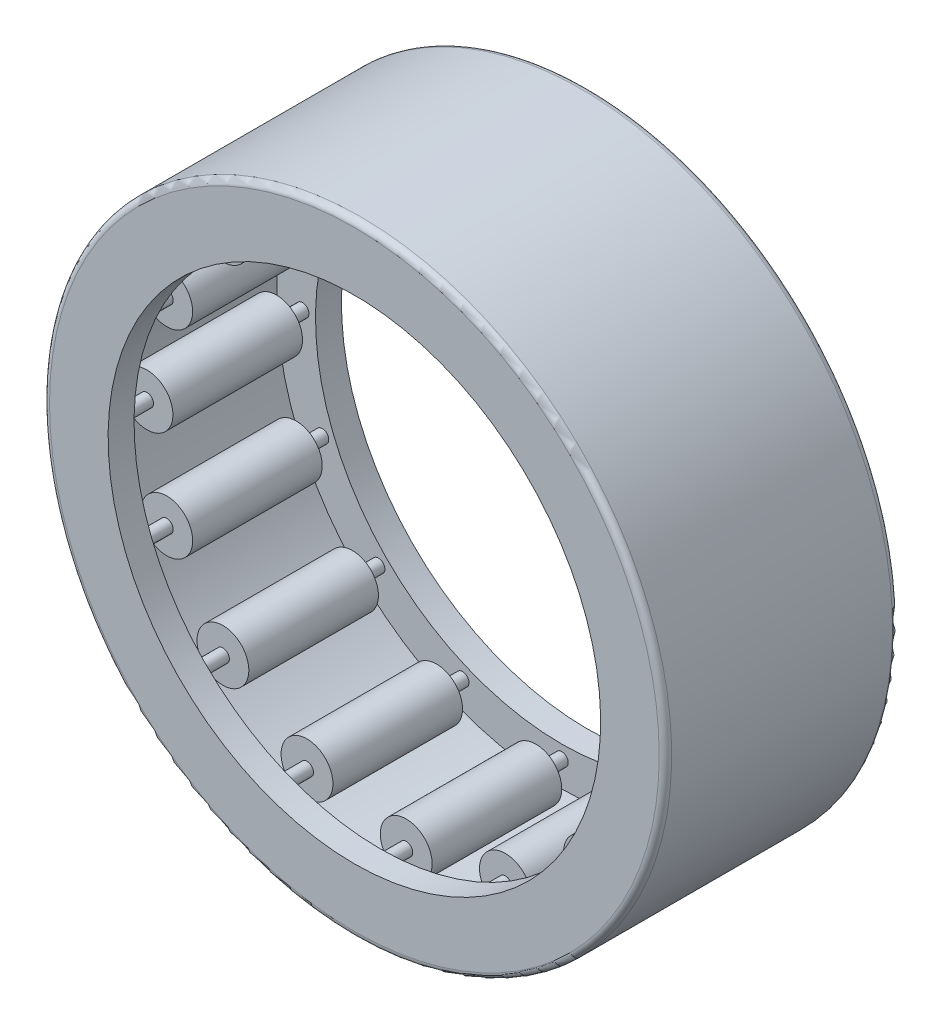
SolidWorks part; units mm, degrees
ref_plane "Front Plane" through (0, 0, 0) normal (0, 0, 1) x (1, 0, 0)
ref_plane "Top Plane" through (0, 0, 0) normal (0, 1, 0) x (1, 0, 0)
ref_plane "Right Plane" through (0, 0, 0) normal (1, 0, 0) x (0, 0, -1)
sketch "Sketch1" plane through (0, 0, 0) normal (1, 0, 0) x (0, 0, -1)
  line L0 (-4.7625, 0) -> (4.7625, 0) construction
  line L1 (0, 0) -> (0, 12.7) construction
  line L2 (-4.7625, 0) -> (-4.7625, 12.7) construction
  line L3 (-4.7625, 12.7) -> (4.7625, 12.7)
  line L4 (4.7625, 12.7) -> (4.7625, 0) construction
  line L5 (4.7625, 0) -> (3.7042, 0) construction
  line L6 (3.7042, 0) -> (3.7042, 11.6417) construction
  line L7 (3.7042, 11.6417) -> (-3.7042, 11.6417)
  line L8 (-3.7042, 11.6417) -> (-3.7042, 0) construction
  line L9 (-3.7042, 0) -> (-4.7625, 0) construction
  line L10 (-4.7625, 12.7) -> (-4.7625, 10.0542)
  line L11 (-4.7625, 10.0542) -> (-3.7042, 10.0542)
  line L12 (-3.7042, 10.0542) -> (-3.7042, 11.6417)
  line L13 (3.7042, 12.7) -> (3.7042, 11.6417) construction
  line L14 (3.7042, 11.6417) -> (3.7042, 10.0542)
  line L15 (3.7042, 10.0542) -> (4.7625, 10.0542)
  line L16 (4.7625, 10.0542) -> (4.7625, 12.7)
  line L17 (3.7042, 11.6417) -> (3.7042, 10.5833) construction
  line L18 (3.7042, 10.5833) -> (3.7042, 9.525) construction
  point P5 (0, 9.525)
  dimension "Width" = 9.525
  dimension "OD" = 25.4
  dimension "Shaft Dia" = 19.05
revolve "Revolve1" add sketch "Sketch1" angle 360 about L0
sketch "Sketch2" plane through (0, 0, 0) normal (1, 0, 0) x (0, 0, -1)
  line L0 (3.7042, 11.6417) -> (-3.7042, 11.6417) construction
  line L1 (-2.6458, 10.5833) -> (2.6458, 10.5833) construction
  line L2 (-2.6458, 10.5833) -> (-2.6458, 11.6417) construction
  line L3 (-2.6458, 11.6417) -> (2.6458, 11.6417)
  line L4 (2.6458, 10.5833) -> (2.6458, 11.6417) construction
  line L5 (3.7042, 10.0542) -> (4.7625, 10.0542) construction
  line L6 (-3.7042, 10.5833) -> (-2.6458, 10.5833) construction
  line L7 (2.6458, 10.5833) -> (3.7042, 10.5833) construction
  line L8 (-4.7625, 10.0542) -> (-3.7042, 10.0542) construction
  line L9 (-2.6458, 10.8479) -> (-2.6458, 10.3187) construction
  line L10 (-3.7042, 10.5833) -> (-3.7042, 10.0542) construction
  line L11 (-2.6458, 11.6417) -> (-2.6458, 10.8479)
  line L12 (2.6458, 11.6417) -> (2.6458, 10.8479)
  line L13 (2.6458, 10.8479) -> (-2.6458, 10.8479)
  line L14 (0, 11.6417) -> (0, 9.525) construction
  line L15 (-3.7042, 10.0542) -> (-3.7042, 11.6417) construction
  line L16 (-2.6458, 10.3187) -> (-3.7042, 10.3187) construction
  line L17 (0, 0) -> (4.7625, 0) construction
  line L31 (4.7625, -12.7) -> (4.7625, 12.7) construction
  point P16 (0, 10.5833)
revolve "Revolve2" add sketch "Sketch2" angle 360 about L1
sketch "Sketch3" plane through (0, 0, 0) normal (1, 0, 0) x (0, 0, -1)
  line L0 (3.7042, 11.6417) -> (3.7042, 10.0542) construction
  line L1 (-3.7042, 10.5833) -> (3.7042, 10.5833)
  line L2 (-3.7042, 10.5833) -> (-3.7042, 10.8479)
  line L3 (-3.7042, 10.8479) -> (3.7042, 10.8479)
  line L4 (3.7042, 10.5833) -> (3.7042, 10.8479)
  line L5 (0, 0) -> (4.7625, 0) construction
  line L6 (4.7625, -12.7) -> (4.7625, 12.7) construction
revolve "Revolve3" add sketch "Sketch3" angle 360 about L1
ref_axis "Axis1" through (0, 0, -4.7625) along (0, 0, 1)
pattern_circular "CirPattern1" count 16 over 360 about axis through (0, 0, -4.7625) along (0, 0, 1) of bodies 166 167
fillet "Fillet1" radius 0.254 2 edges at (0, -12.7, -4.7625) (0, -12.7, 4.7625)
sketch "Sketch4" plane through (0, 0, 0) normal (1, 0, 0) x (0, 0, -1)
  line L1 (4.5085, 9.525) -> (2.6458, 9.525)
  line L2 (4.5085, 9.525) -> (4.5085, 10.0542)
  line L3 (4.5085, 10.0542) -> (2.6458, 10.0542)
  line L4 (2.6458, 9.525) -> (2.6458, 10.0542)
  line L5 (-4.7625, 10.0542) -> (-3.7042, 10.0542) construction
  line L6 (4.5085, -12.7) -> (4.5085, 12.7) construction
  line L7 (2.6458, 11.6417) -> (2.6458, 10.8479) construction
revolve "Revolve4" [suppressed] add sketch "Sketch4" angle 360 about L0
sketch "Sketch5" plane through (0, 0, 0) normal (1, 0, 0) x (0, 0, -1)
  line L0 (-4.5085, 12.7) -> (-4.5085, -12.7) construction
  line L1 (-2.6458, 9.525) -> (-4.5085, 9.525)
  line L2 (-2.6458, 9.525) -> (-2.6458, 10.0542)
  line L3 (-2.6458, 10.0542) -> (-4.5085, 10.0542)
  line L4 (-4.5085, 9.525) -> (-4.5085, 10.0542)
  line L6 (-2.6458, 11.6417) -> (-2.6458, 10.8479) construction
  line L7 (-4.7625, 10.0542) -> (-3.7042, 10.0542) construction
revolve "Revolve5" [suppressed] add sketch "Sketch5" angle 360 about L0
sketch "Front View" plane through (0, 0, 0) normal (0, 0, 1) x (1, 0, 0)
  circle A0 centre (0, 0) radius 9.525 construction
  circle A1 centre (0, 0) radius 12.7 construction
  dimension "OD" = 25.4
  dimension "ID" = 19.05
sketch "Right View" plane through (0, 0, 0) normal (1, 0, 0) x (0, 0, -1)
  line L0 (-4.7625, 12.7) -> (4.7625, 12.7) construction
  dimension "Width" = 9.525
ref_axis "Center Axis 1" through (0, 0, -4.5085) along (0, 0, 1)
ref_plane "Contact Plane 1" through (0, 0, 4.7625) normal (0, 0, 1) x (1, 0, 0)
ref_plane "Contact Plane 2" through (0, 0, -4.7625) normal (0, 0, -1) x (-1, 0, 0)
equation "\"Rollers@CirPattern1\" = \"OD@Sketch1\"*16"
equation "\"D1@Fillet1\" = \"OD@Sketch1\"*.01"
equation "\"Angle@CirPattern1\"= 360 / \"Rollers@CirPattern1\""
equation "\"OD@Front View\"=\"OD@Sketch1\""
equation "\"ID@Front View\"=\"Shaft Dia@Sketch1\""
equation "\"Width@Right View\"=\"Width@Sketch1\""
